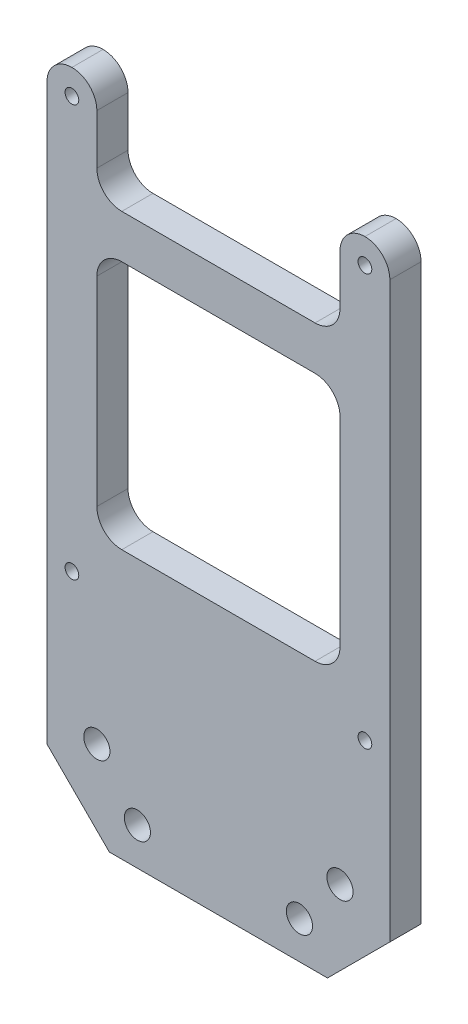
SolidWorks part; units mm, degrees
ref_plane "前视基准面" through (0, 0, 0) normal (0, 0, 1) x (1, 0, 0)
ref_plane "上视基准面" through (0, 0, 0) normal (0, 1, 0) x (1, 0, 0)
ref_plane "右视基准面" through (0, 0, 0) normal (1, 0, 0) x (0, 0, -1)
sketch "草图1" plane through (0, 0, 0) normal (0, 0, 1) x (1, 0, 0)
  line L0 (-27.5, 53) -> (-27.5, 49) construction
  line L1 (-27.5, 53) -> (27.5, 53)
  line L2 (-27.5, 53) -> (-27.5, -53)
  line L3 (-27.5, -53) -> (27.5, -53)
  line L4 (27.5, 53) -> (27.5, -53)
  line L5 (-27.5, 53) -> (27.5, -53) construction
  line L6 (-27.5, -53) -> (27.5, 53) construction
  line L7 (-27.5, 49) -> (-23.5, 49) construction
  line L8 (0, 0) -> (0, 10) construction
  line L9 (0, 0) -> (10, 0) construction
  line L10 (-23.5, 49) -> (-23.5, -17) construction
  circle A0 centre (-23.5, 49) radius 1.1
  circle A1 centre (23.5, 49) radius 1.1
  circle A2 centre (-23.5, -17) radius 1.1
  circle A3 centre (23.5, -17) radius 1.1
  point P0 (0, 0)
  dimension "D1" = 55
  dimension "D2" = 106
extrude "凸台-拉伸1" add sketch "草图1" along normal blind 5
chamfer "倒角1" distance 10 angle 45 2 edges at (-27.5, -53, 2.5) (27.5, -53, 2.5)
fillet "圆角1" radius 4 2 edges at (27.5, 53, 2.5) (-27.5, 53, 2.5)
sketch "草图4" plane through (0, 0, 0) normal (0, 0, -1) x (-1, 0, 0)
  line L0 (0, -53) -> (-13, -53) construction
  line L1 (17.5, -53) -> (-17.5, -53) construction
  line L2 (-13, -53) -> (-13, -47) construction
  line L3 (-13, -47) -> (-13, -39) construction
  line L4 (-13, -39) -> (-19.5, -39) construction
  line L5 (0, -53) -> (0, -43) construction
  circle A0 centre (-13, -47) radius 2.1
  circle A1 centre (-19.5, -39) radius 2.1
  circle A2 centre (19.5, -39) radius 2.1
  circle A3 centre (13, -47) radius 2.1
extrude "切除-拉伸1" cut sketch "草图4" against normal blind 10
sketch "草图5" plane through (0, 0, 5) normal (0, 0, 1) x (1, 0, 0)
  line L0 (0, 0) -> (0, 53) construction
  line L1 (23.5, 53) -> (-23.5, 53) construction
  line L2 (19.5, 53) -> (-19.5, 53)
  line L3 (-19.5, 53) -> (-19.5, 45)
  line L4 (-19.5, 45) -> (-19.5, 37)
  line L5 (-19.5, 37) -> (19.5, 37)
  line L6 (19.5, 53) -> (19.5, 45)
  line L7 (19.5, 45) -> (19.5, 37)
  point P13 (0, 37)
extrude "切除-拉伸2" cut sketch "草图5" against normal blind 10
fillet "圆角2" radius 4 4 edges at (-19.5, 37, 2.5) (19.5, 37, 2.5) (19.5, 53, 2.5) (-19.5, 53, 2.5)
sketch "草图6" plane through (0, 0, 5) normal (0, 0, 1) x (1, 0, 0)
  line L0 (-23.5, -17) -> (-23.5, 16) construction
  line L1 (-23.5, 16) -> (0, 16) construction
  line L2 (0, 0) -> (0, 10) construction
  line L4 (-19.5, 30) -> (19.5, 30)
  line L5 (-19.5, 30) -> (-19.5, -10)
  line L6 (-19.5, -10) -> (19.5, -10)
  line L7 (19.5, 30) -> (19.5, -10)
  line L8 (-19.5, 30) -> (19.5, -10) construction
  line L9 (-19.5, -10) -> (19.5, 30) construction
extrude "切除-拉伸3" cut sketch "草图6" against normal blind 10
fillet "圆角3" radius 4 4 edges at (-19.5, -10, 2.5) (19.5, -10, 2.5) (19.5, 30, 2.5) (-19.5, 30, 2.5)
